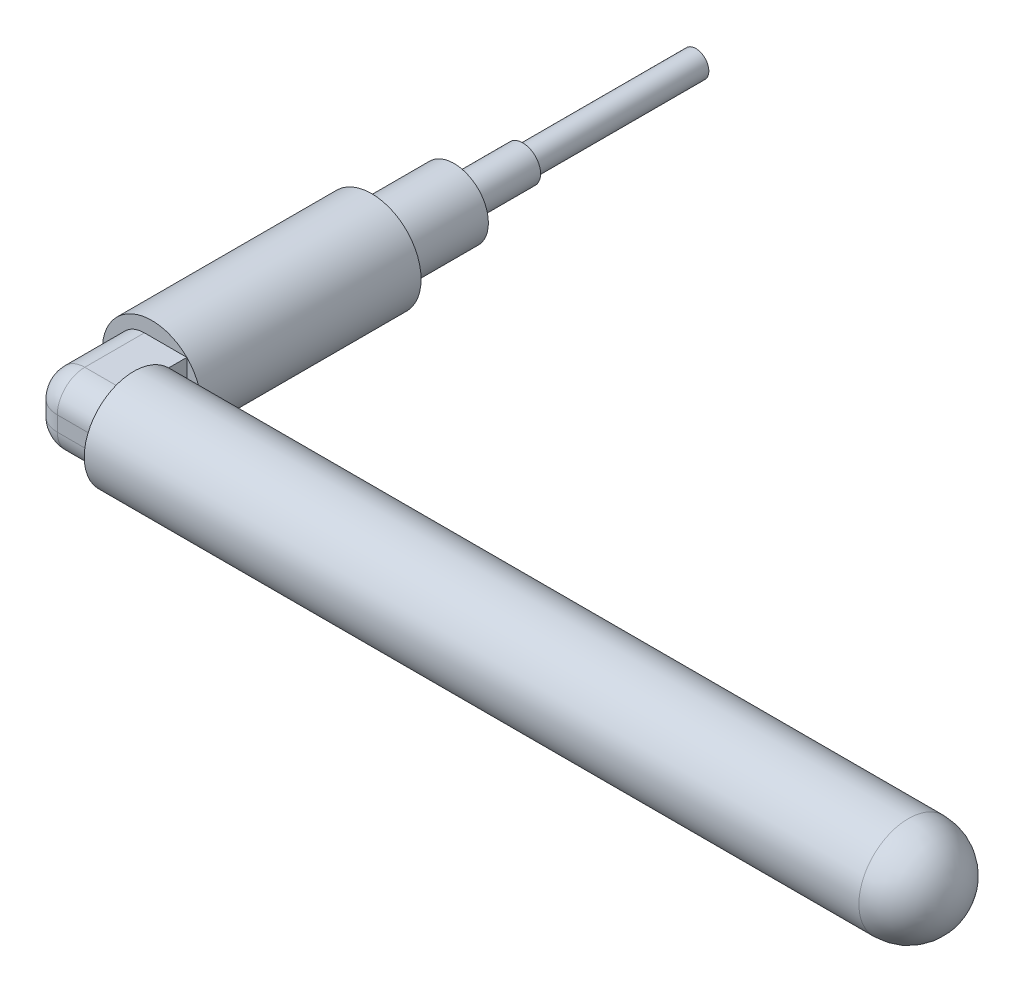
SolidWorks part; units mm, degrees
ref_plane "Front Plane" through (0, 0, 0) normal (0, 0, 1) x (1, 0, 0)
ref_plane "Top Plane" through (0, 0, 0) normal (0, 1, 0) x (1, 0, 0)
ref_plane "Right Plane" through (0, 0, 0) normal (1, 0, 0) x (0, 0, -1)
sketch "Sketch1" plane through (0, 0, 0) normal (0, 0, 1) x (1, 0, 0)
  circle A0 centre (0, 0) radius 4.572
  dimension "D1" = 9.144
extrude "Boss-Extrude1" add sketch "Sketch1" along normal blind 20.32
sketch "Sketch2" plane through (0, 0, 0) normal (0, 0, -1) x (-1, 0, 0)
  circle A0 centre (0, 0) radius 3.175
  circle A1 centre (0, 0) radius 4.572 construction
  dimension "D1" = 6.35
extrude "Boss-Extrude2" add sketch "Sketch2" along normal blind 7.62
sketch "Sketch3" plane through (0, 0, -7.62) normal (0, 0, -1) x (-1, 0, 0)
  circle A0 centre (0, 0) radius 1.651
  circle A1 centre (0, 0) radius 3.175 construction
  dimension "D1" = 3.302
extrude "Boss-Extrude3" add sketch "Sketch3" along normal blind 6.35
sketch "Sketch4" plane through (0, 0, -13.97) normal (0, 0, -1) x (-1, 0, 0)
  circle A0 centre (0, 0) radius 1.2065
  circle A1 centre (0, 0) radius 1.651 construction
  dimension "D1" = 2.413
extrude "Boss-Extrude4" add sketch "Sketch4" along normal blind 16.002
sketch "Sketch8" plane through (0, 0, 20.32) normal (0, 0, 1) x (1, 0, 0)
  line L1 (3.2329, -3.2329) -> (-3.2329, -3.2329)
  line L2 (3.2329, -3.2329) -> (3.2329, 3.2329)
  line L3 (3.2329, 3.2329) -> (-3.2329, 3.2329)
  line L4 (-3.2329, -3.2329) -> (-3.2329, 3.2329)
  circle A1 centre (0, 0) radius 4.572 construction
  point P6 (0, 0)
extrude "Boss-Extrude5" add sketch "Sketch8" along normal blind 8.0518
sketch "Sketch10" plane through (3.2329, 0, 0) normal (1, 0, 0) x (0, 0, -1)
  line L0 (-28.3718, 0) -> (-22.098, 0) construction
  line L2 (-22.098, 0) -> (-20.32, 0) construction
  line L3 (-28.3718, -3.2329) -> (-28.3718, 3.2329) construction
  line L5 (-20.32, -3.2329) -> (-20.32, 3.2329) construction
  circle A0 centre (-25.2349, 0) radius 4.572
  dimension "D2" = 9.144
  dimension "D1" = 1.778
extrude "Boss-Extrude6" add sketch "Sketch10" along normal blind 71.628
dome "Dome4" faces to dome 1 distance 4.572 reverse direction no elliptical dome no face at (74.8609, 4.572, 25.2349) parameters "D1"=4.572
fillet "Fillet1" radius 2.54 5 edges at (0, -3.2329, 28.3718) (-3.2329, -3.2329, 24.3459) (-3.2329, 3.2329, 24.3459) (0, 3.2329, 28.3718) (-3.2329, 0, 28.3718)
